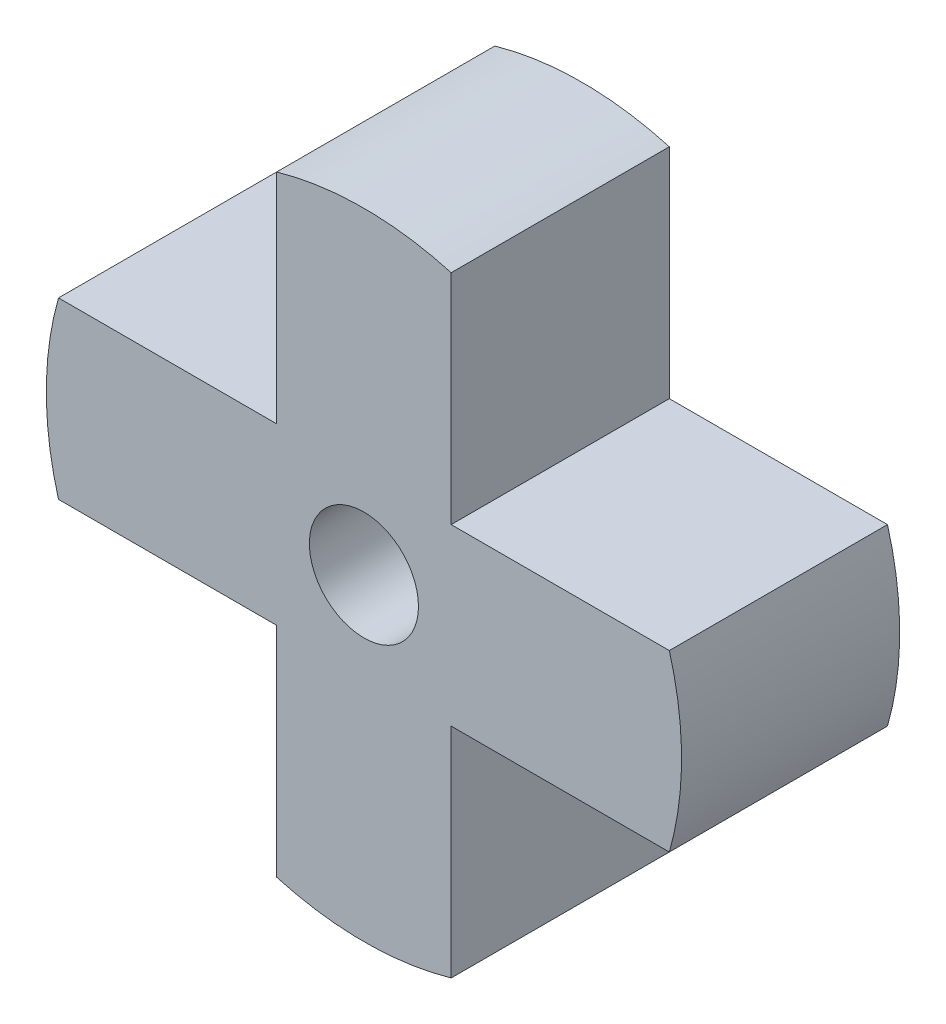
SolidWorks part; units mm, degrees
ref_plane "Front Plane" through (0, 0, 0) normal (0, 0, 1) x (1, 0, 0)
ref_plane "Top Plane" through (0, 0, 0) normal (0, 1, 0) x (1, 0, 0)
ref_plane "Right Plane" through (0, 0, 0) normal (1, 0, 0) x (0, 0, -1)
sketch "Sketch1" plane through (0, 0, 0) normal (0, 0, 1) x (1, 0, 0)
  line L0 (0, 0) -> (7, 0) construction
  line L1 (-7, 0) -> (0, 0) construction
  line L2 (0, 7) -> (0, 0) construction
  line L3 (0, -7) -> (0, 0) construction
  line L4 (0, -2) -> (7, -2)
  line L5 (-2, 7) -> (-2, 0)
  line L6 (-7, -2) -> (0, -2)
  line L7 (2, -7) -> (2, 0)
  line L8 (0, 2) -> (7, 2)
  line L9 (2, 7) -> (2, 0)
  line L10 (-7, 2) -> (0, 2)
  line L11 (-2, -7) -> (-2, 0)
  circle A0 centre (0, 0) radius 7 construction
  circle A1 centre (0, 0) radius 1.25
  circle A2 centre (0, 0) radius 7.2801
  dimension "D1" = 2.5
  dimension "D2" = 14
  dimension "D3" = 2
  dimension "D4" = 2
extrude "Boss-Extrude1" add sketch "Sketch1" along normal blind 5 contours L10 A2 L6 L11 L5 | L9 A2 L5 L10 L8 | L11 L6 L4 L7 L9 L8 L10 L5 A1 | L11 A2 L7 L4 L6 | L4 A2 L8 L9 L7 region at (-1, -1.9434, 0) region at (0, -4.5944, 0) region at (4.5944, 0, 0) region at (-4.5944, 0, 0) region at (0, 4.5944, 0)
